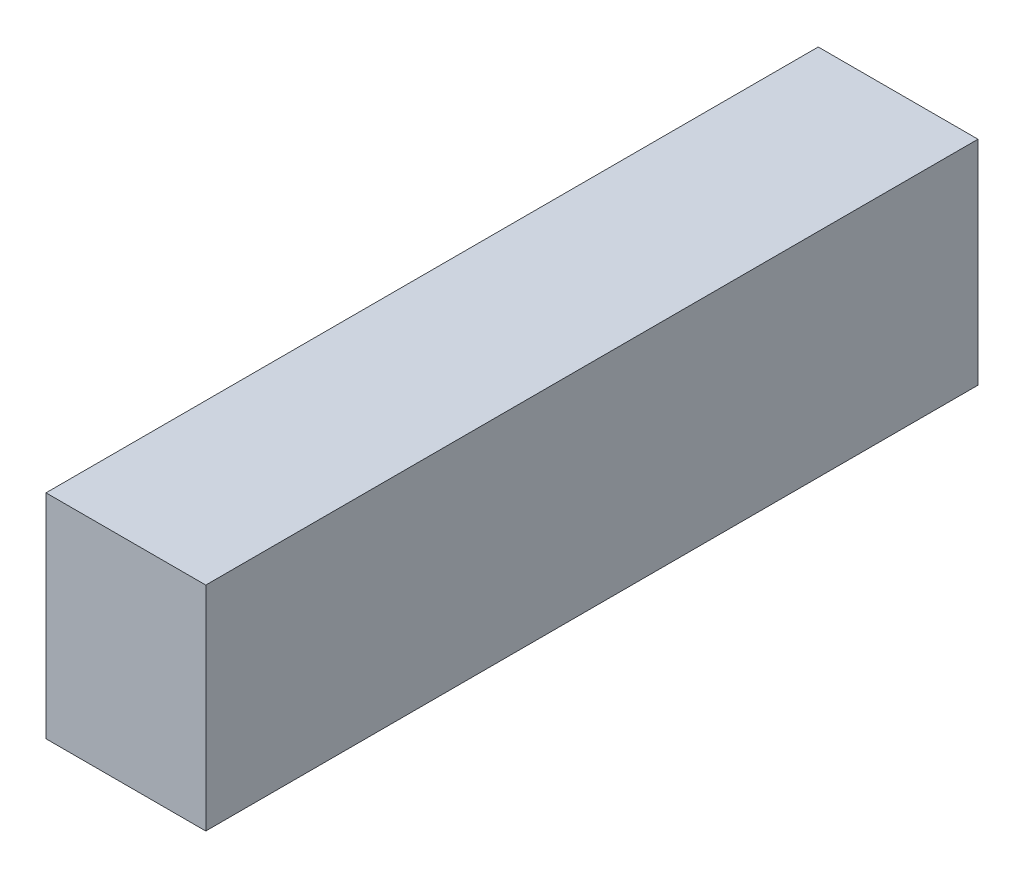
SolidWorks part; units mm, degrees
ref_plane "Front Plane" through (0, 0, 0) normal (0, 0, 1) x (1, 0, 0)
ref_plane "Top Plane" through (0, 0, 0) normal (0, 1, 0) x (1, 0, 0)
ref_plane "Right Plane" through (0, 0, 0) normal (1, 0, 0) x (0, 0, -1)
sketch "Sketch3" plane through (0, 0, 120) normal (0, 0, 1) x (1, 0, 0)
  line L1 (-120, 0) -> (-180, 0)
  line L2 (-180, 0) -> (-180, 80)
  line L3 (-180, 80) -> (-120, 80)
  line L4 (-120, 200) -> (-120, 0) construction
  line L5 (-120, 80) -> (-120, 0)
  dimension "D1" = 60
  dimension "D2" = 80
extrude "Boss-Extrude1" add sketch "Sketch3" along normal blind 25 contours L3 L5 L1 L2
sketch "Sketch4" plane through (0, 0, -120) normal (0, 0, -1) x (-1, 0, 0)
  line L1 (120, 80) -> (180, 80)
  line L2 (180, 80) -> (180, 0)
  line L3 (180, 0) -> (120, 0)
  line L4 (120, 0) -> (120, 80)
extrude "Boss-Extrude2" add sketch "Sketch4" along normal blind 25 separate body
sketch "Sketch5" plane through (0, 0, 120) normal (0, 0, -1) x (-1, 0, 0)
  line L0 (120, 80) -> (180, 0)
  line L1 (180, 0) -> (120, 0)
  line L2 (120, 0) -> (120, 80)
extrude "Boss-Extrude3" add sketch "Sketch5" along normal up to surface (240 mm away) up to face at (-150, 40, -120)
sketch "Sketch6" plane through (0, 0, 120) normal (0, 0, -1) x (-1, 0, 0)
  line L0 (120, 80) -> (180, 80)
  line L1 (180, 80) -> (120, 0)
  line L2 (120, 0) -> (120, 80)
extrude "Boss-Extrude4" add sketch "Sketch6" along normal up to surface (240 mm away) up to face at (-160, 53.3333, -120)
